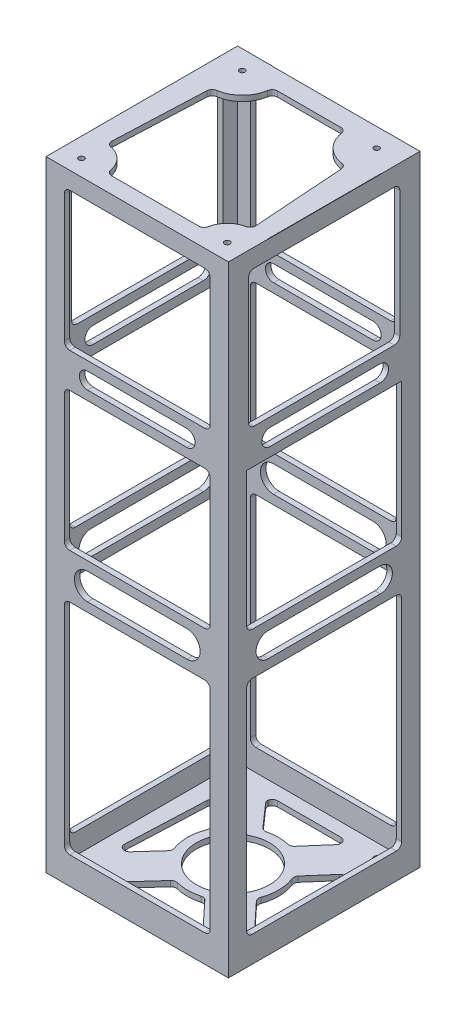
SolidWorks part; units mm, degrees
material "1060 Alloy"
ref_plane "Front Plane" through (0, 0, 0) normal (0, 0, 1) x (1, 0, 0)
ref_plane "Top Plane" through (0, 0, 0) normal (0, 1, 0) x (1, 0, 0)
ref_plane "Right Plane" through (0, 0, 0) normal (1, 0, 0) x (0, 0, -1)
sketch "Sketch1" plane through (0, 0, 0) normal (0, 1, 0) x (1, 0, 0)
  line L1 (-50, -52.5) -> (50, -52.5)
  line L2 (-50, -52.5) -> (-50, 52.5)
  line L3 (-50, 52.5) -> (50, 52.5)
  line L4 (50, -52.5) -> (50, 52.5)
  line L5 (-50, -52.5) -> (50, 52.5) construction
  line L6 (-50, 52.5) -> (50, -52.5) construction
  point P0 (0, 0)
  dimension "D1" = 100
  dimension "D2" = 105
extrude "Body" add sketch "Sketch1" along normal blind 337
shell "Shell1" thickness 3 removed face at (0, 0, 0)
sketch "Sketch8" plane through (0, 0, 0) normal (0, -1, 0) x (1, 0, 0)
  line L1 (-50, 52.5) -> (50, 52.5)
  line L2 (-50, 52.5) -> (-50, -52.5)
  line L3 (-50, -52.5) -> (50, -52.5)
  line L4 (50, 52.5) -> (50, -52.5)
  line L5 (-50, 52.5) -> (50, -52.5) construction
  line L6 (-50, -52.5) -> (50, 52.5) construction
  circle A0 centre (0, 0) radius 20
  point P4 (0, 0)
  dimension "D1" = 40
extrude "ScopeEnd" add sketch "Sketch8" along normal blind 3
sketch "Sketch5" plane through (0, 334, 0) normal (0, -1, 0) x (1, 0, 0)
  line L0 (49.9999, -52.4997) -> (-50.0001, 52.5003) construction
  line L1 (-50.0001, 52.5003) -> (-50.0001, -52.4997) construction
  line L2 (-50.0001, -52.4997) -> (49.9999, 52.5003) construction
  line L5 (45.6309, 48.6491) -> (-44.5391, -47.2409) construction
  line L6 (52.5, 50.0002) -> (52.5, -49.9998) construction
  line L7 (50, -52.4998) -> (50, 52.5002) construction
  line L8 (50, 52.5002) -> (-50, 52.5002) construction
  line L9 (-50, -52.4998) -> (-50, 52.5002) construction
  line L10 (50, -52.4998) -> (-50, 52.5002) construction
  line L11 (50, 52.5002) -> (-50, -52.4998) construction
  line L12 (-44.5391, -47.2409) -> (-44.5391, 48.6491) construction
  line L13 (0, 0.0002) -> (0, -67.3948) construction
  circle A0 centre (36.6309, -42.1409) radius 1.5
  circle A1 centre (-37.0391, -42.1409) radius 1.5
  circle A2 centre (-39.4391, 43.6491) radius 1.5
  circle A3 centre (40.5309, 43.6491) radius 1.5
  point P4 (-0.0001, 0.0003)
  point P17 (0, 0.0002)
  dimension "D1" = 3
  dimension "D2" = 3
extrude "AluHoles" cut sketch "Sketch5" against normal through all both and the other way through all
sketch "Sketch6" plane through (0, 337, 0) normal (0, 1, 0) x (1, 0, 0)
  line L0 (-37.0391, 25.5488) -> (-39.4391, -29.8697)
  line L1 (-25.6597, -43.6491) -> (27.5694, -43.6491)
  line L2 (-20.447, 42.1409) -> (19.7181, 42.1409)
  line L3 (36.6309, 25.2281) -> (40.5309, -30.6876)
  arc A0 (-37.0391, 25.5488) -> (-20.447, 42.1409) centre (-37.0391, 42.1409) ccw
  arc A1 (19.7181, 42.1409) -> (36.6309, 25.2281) centre (36.6309, 42.1409) ccw
  arc A2 (40.5309, -30.6876) -> (27.5694, -43.6491) centre (40.5309, -43.6491) ccw
  arc A3 (-25.6597, -43.6491) -> (-39.4391, -29.8697) centre (-39.4391, -43.6491) ccw
extrude "Cut-Extrude3" cut sketch "Sketch6" against normal blind 3
fillet "Fillet1" radius 3 8 edges at (-39.4391, 335.5, 29.8697) (-25.6597, 335.5, 43.6491) (27.5694, 335.5, 43.6491) (40.5309, 335.5, 30.6876) (36.6309, 335.5, -25.2281) (19.7181, 335.5, -42.1409) (-37.0391, 335.5, -25.5488) (-20.447, 335.5, -42.1409)
sketch "Sketch9" plane through (0, 0, 52.5) normal (0, 0, 1) x (1, 0, 0)
  line L1 (-50, 337) -> (50, 337) construction
  line L2 (-50, 337) -> (-50, -3) construction
  line L3 (-50, -3) -> (50, -3) construction
  line L4 (50, 337) -> (50, -3) construction
  line L5 (-50, 337) -> (50, -3) construction
  line L6 (-50, -3) -> (50, 337) construction
  line L7 (-50, 337) -> (50, 337) construction
  line L8 (-50, 337) -> (-50, 242) construction
  line L9 (-50, 242) -> (50, 242) construction
  line L10 (50, 337) -> (50, 242) construction
  line L11 (-50, 337) -> (50, 242) construction
  line L12 (-50, 242) -> (50, 337) construction
  line L13 (-50, 242) -> (50, 242)
  line L14 (-50, 242) -> (-50, 147) construction
  line L15 (-50, 147) -> (50, 147) construction
  line L16 (50, 242) -> (50, 147) construction
  line L17 (-50, 242) -> (50, 147) construction
  line L18 (-50, 147) -> (50, 242) construction
  line L19 (-50, 147) -> (50, 147) construction
  line L20 (-50, 147) -> (-50, -3) construction
  line L21 (-50, -3) -> (50, -3) construction
  line L22 (50, 147) -> (50, -3) construction
  line L23 (-50, 147) -> (50, -3) construction
  line L24 (-50, -3) -> (50, 147) construction
  line L25 (-40, 251.5) -> (40, 251.5)
  line L26 (-40, 251.5) -> (-40, 327.5)
  line L27 (-40, 327.5) -> (40, 327.5)
  line L28 (40, 251.5) -> (40, 327.5)
  line L29 (-40, 251.5) -> (40, 327.5) construction
  line L30 (-40, 327.5) -> (40, 251.5) construction
  line L31 (-40, 156.5) -> (40, 156.5)
  line L32 (-40, 156.5) -> (-40, 232.5)
  line L33 (-40, 232.5) -> (40, 232.5)
  line L34 (40, 156.5) -> (40, 232.5)
  line L35 (-40, 156.5) -> (40, 232.5) construction
  line L36 (-40, 232.5) -> (40, 156.5) construction
  line L37 (-40, 12) -> (40, 12)
  line L38 (-40, 12) -> (-40, 132)
  line L39 (-40, 132) -> (40, 132)
  line L40 (40, 12) -> (40, 132)
  line L41 (-40, 12) -> (40, 132) construction
  line L42 (-40, 132) -> (40, 12) construction
  point P4 (0, 167)
  point P9 (0, 289.5)
  point P12 (0, 194.5)
  point P13 (0, 289.5)
  point P14 (0, 72)
  point P19 (0, 194.5)
  point P24 (0, 72)
  dimension "D1" = 150
  dimension "D2" = 95
  dimension "D3" = 95
  dimension "D4" = 10
  dimension "D5" = 10
  dimension "D6" = 10
extrude "Cut-Extrude4" cut sketch "Sketch9" against normal through all contours L31 L34 L33 L32 | L25 L28 L27 L26 | L37 L40 L39 L38 region at (0, 289.5, 52.5) region at (0, 194.5, 52.5) region at (0, 72, 52.5)
sketch "Sketch10" plane through (50, 0, 0) normal (1, 0, 0) x (0, 0, -1)
  line L0 (52.5, 337) -> (52.5, -3) construction
  line L1 (-52.5, 337) -> (52.5, 337) construction
  line L2 (-52.5, 337) -> (-52.5, 242) construction
  line L3 (-52.5, 242) -> (52.5, 242) construction
  line L4 (52.5, 337) -> (52.5, 242) construction
  line L5 (-52.5, 337) -> (52.5, 242) construction
  line L6 (-52.5, 242) -> (52.5, 337) construction
  line L7 (-52.5, 337) -> (-52.5, -3) construction
  line L8 (52.5, 242) -> (-52.5, 242) construction
  line L9 (52.5, 242) -> (52.5, 147) construction
  line L10 (52.5, 147) -> (-52.5, 147) construction
  line L11 (-52.5, 242) -> (-52.5, 147) construction
  line L12 (52.5, 242) -> (-52.5, 147) construction
  line L13 (52.5, 147) -> (-52.5, 242) construction
  line L15 (42.5, 156.0476) -> (-42.5, 156.0476)
  line L16 (42.5, 156.0476) -> (42.5, 232.9524)
  line L17 (42.5, 232.9524) -> (-42.5, 232.9524)
  line L18 (-42.5, 156.0476) -> (-42.5, 232.9524)
  line L19 (42.5, 156.0476) -> (-42.5, 232.9524) construction
  line L20 (42.5, 232.9524) -> (-42.5, 156.0476) construction
  line L21 (41.4474, 252) -> (-41.4474, 252)
  line L22 (41.4474, 252) -> (41.4474, 327)
  line L23 (41.4474, 327) -> (-41.4474, 327)
  line L24 (-41.4474, 252) -> (-41.4474, 327)
  line L25 (41.4474, 252) -> (-41.4474, 327) construction
  line L26 (41.4474, 327) -> (-41.4474, 252) construction
  line L27 (-52.5, 147) -> (52.5, 147) construction
  line L28 (-52.5, 147) -> (-52.5, -3) construction
  line L29 (-52.5, -3) -> (52.5, -3) construction
  line L30 (52.5, 147) -> (52.5, -3) construction
  line L31 (-52.5, 147) -> (52.5, -3) construction
  line L32 (-52.5, -3) -> (52.5, 147) construction
  line L33 (-42.5, 11.2857) -> (42.5, 11.2857)
  line L34 (-42.5, 11.2857) -> (-42.5, 132.7143)
  line L35 (-42.5, 132.7143) -> (42.5, 132.7143)
  line L36 (42.5, 11.2857) -> (42.5, 132.7143)
  line L37 (-42.5, 11.2857) -> (42.5, 132.7143) construction
  line L38 (-42.5, 132.7143) -> (42.5, 11.2857) construction
  point P4 (0, 289.5)
  point P10 (0, 194.5)
  point P13 (0, 194.5)
  point P18 (0, 289.5)
  point P25 (0, 72)
  point P27 (0, 72)
  dimension "D1" = 95
  dimension "D2" = 95
  dimension "D3" = 10
  dimension "D4" = 10
extrude "Cut-Extrude5" cut sketch "Sketch10" against normal through all
fillet "Fillet2" radius 3 45 edges at (-48.5, 132.7143, -42.5) (-48.5, 11.2857, 42.5) (48.5, 11.2857, 42.5) (40, 12, 51) (48.5, 11.2857, -42.5) (40, 12, -51) (48.5, 132.7143, -42.5) (40, 132, 51) (40, 132, -51) (-40, 132, -51) (-40, 132, 51) (-48.5, 132.7143, 42.5) (48.5, 132.7143, 42.5) (-48.5, 232.9524, -42.5) (40, 232.5, -51) (-40, 232.5, -51) (-40, 156.5, -51) (48.5, 156.0476, 42.5) (-48.5, 156.0476, 42.5) (-48.5, 11.2857, -42.5) (-48.5, 156.0476, -42.5) (40, 156.5, -51) (48.5, 156.0476, -42.5) (40, 156.5, 51) (-40, 156.5, 51) (-40, 232.5, 51) (40, 232.5, 51) (40, 327.5, 51) (48.5, 252, -41.4474) (-48.5, 252, -41.4474) (-40, 251.5, -51) (40, 251.5, -51) (40, 251.5, 51) (40, 327.5, -51) (48.5, 327, -41.4474) (-48.5, 327, -41.4474) (-40, 327.5, -51) (-48.5, 327, 41.4474) (48.5, 327, 41.4474) (-40, 327.5, 51) (-48.5, 252, 41.4474) (-40, 251.5, 51) (48.5, 252, 41.4474) (-40, 12, 51) (-40, 12, -51)
sketch "Sketch11" plane through (0, 0, -52.5) normal (0, 0, -1) x (-1, 0, 0)
  line L0 (-31.11, 337) -> (31.11, 337) construction
  line L1 (-50, 337) -> (50, 337) construction
  line L2 (0, 0) -> (0, 50000) construction
  line L3 (-31.11, 337) -> (31.11, 337)
  line L4 (-31.11, 337) -> (-31.11, 336.9)
  line L5 (-31.11, 336.9) -> (31.11, 336.9)
  line L6 (31.11, 337) -> (31.11, 336.9)
  line L7 (-31.11, 337) -> (31.11, 336.9) construction
  line L8 (-31.11, 336.9) -> (31.11, 337) construction
  point P5 (0, 337)
  point P7 (0, 336.95)
  dimension "D1" = 62.22
  dimension "D2" = 0.1
  dimension "D3" = 0
extrude "Cut-Extrude6" cut sketch "Sketch11" against normal blind 0.1
sketch "Sketch12" plane through (50, 0, 0) normal (1, 0, 0) x (0, 0, -1)
  line L0 (-31.11, 337) -> (31.11, 337) construction
  line L1 (-52.5, 337) -> (52.5, 337) construction
  line L2 (0, 0) -> (0, 50000) construction
  line L4 (-31.11, 337) -> (31.11, 337)
  line L5 (-31.11, 337) -> (-31.11, 336.9)
  line L6 (-31.11, 336.9) -> (31.11, 336.9)
  line L7 (31.11, 337) -> (31.11, 336.9)
  line L8 (-31.11, 337) -> (31.11, 336.9) construction
  line L9 (-31.11, 336.9) -> (31.11, 337) construction
  point P5 (0, 337)
  point P10 (0, 336.95)
  dimension "D1" = 62.22
  dimension "D2" = 0
  dimension "D3" = 0.1
extrude "Cut-Extrude7" cut sketch "Sketch12" against normal blind 0.1
sketch "Sketch13" plane through (0, 0, -52.5) normal (0, 0, -1) x (-1, 0, 0)
  line L0 (-27.2161, 242) -> (27.2161, 242) construction
  line L1 (-37, 156.5) -> (37, 156.5) construction
  line L2 (-37, 156.5) -> (-37, 132) construction
  line L3 (-37, 132) -> (37, 132) construction
  line L4 (37, 156.5) -> (37, 132) construction
  line L5 (-37, 156.5) -> (37, 132) construction
  line L6 (-37, 132) -> (37, 156.5) construction
  line L7 (-37, 251.5) -> (37, 251.5) construction
  line L8 (-37, 251.5) -> (-37, 232.5) construction
  line L9 (-37, 232.5) -> (37, 232.5) construction
  line L10 (37, 251.5) -> (37, 232.5) construction
  line L11 (-37, 251.5) -> (37, 232.5) construction
  line L12 (-37, 232.5) -> (37, 251.5) construction
  line L13 (-27.2161, 246.5) -> (27.2161, 246.5)
  line L14 (-27.2161, 237.5) -> (27.2161, 237.5)
  line L15 (-27.2161, 144.25) -> (27.2161, 144.25) construction
  line L16 (-27.2161, 151.5) -> (27.2161, 151.5)
  line L17 (-27.2161, 137) -> (27.2161, 137)
  arc A0 (-27.2161, 246.5) -> (-27.2161, 237.5) centre (-27.2161, 242) ccw
  arc A1 (27.2161, 237.5) -> (27.2161, 246.5) centre (27.2161, 242) ccw
  arc A2 (-27.2161, 151.5) -> (-27.2161, 137) centre (-27.2161, 144.25) ccw
  arc A3 (27.2161, 137) -> (27.2161, 151.5) centre (27.2161, 144.25) ccw
  point P4 (0, 144.25)
  point P11 (0, 242)
  point P16 (0, 242)
  point P22 (0, 144.25)
  dimension "D1" = 5
  dimension "D2" = 5
extrude "Cut-Extrude8" cut sketch "Sketch13" against normal through all
sketch "Sketch14" plane through (50, 0, 0) normal (1, 0, 0) x (0, 0, -1)
  line L0 (42.5, 232.9524) -> (-42.5, 232.9524) construction
  line L1 (-38.4474, 252) -> (39.5, 252) construction
  line L2 (-38.4474, 252) -> (-38.4474, 232.9524) construction
  line L3 (-38.4474, 232.9524) -> (39.5, 232.9524) construction
  line L4 (39.5, 252) -> (39.5, 232.9524) construction
  line L5 (-38.4474, 252) -> (39.5, 232.9524) construction
  line L6 (-38.4474, 232.9524) -> (39.5, 252) construction
  line L7 (-29.6655, 242.4762) -> (30.7181, 242.4762) construction
  line L8 (-39.5, 156.0476) -> (39.5, 156.0476) construction
  line L9 (-39.5, 156.0476) -> (-39.5, 132.7143) construction
  line L10 (-39.5, 132.7143) -> (39.5, 132.7143) construction
  line L11 (39.5, 156.0476) -> (39.5, 132.7143) construction
  line L12 (-39.5, 156.0476) -> (39.5, 132.7143) construction
  line L13 (-39.5, 132.7143) -> (39.5, 156.0476) construction
  line L14 (-29.6655, 247) -> (30.7181, 247)
  line L15 (-29.6655, 237.9524) -> (30.7181, 237.9524)
  line L16 (-30.7181, 144.381) -> (30.7181, 144.381) construction
  line L17 (-30.7181, 151.0476) -> (30.7181, 151.0476)
  line L18 (-30.7181, 137.7143) -> (30.7181, 137.7143)
  arc A0 (42.5, 229.9524) -> (39.5, 232.9524) centre (39.5, 229.9524) ccw construction
  arc A1 (-29.6655, 247) -> (-29.6655, 237.9524) centre (-29.6655, 242.4762) ccw
  arc A2 (30.7181, 237.9524) -> (30.7181, 247) centre (30.7181, 242.4762) ccw
  arc A3 (-30.7181, 151.0476) -> (-30.7181, 137.7143) centre (-30.7181, 144.381) ccw
  arc A4 (30.7181, 137.7143) -> (30.7181, 151.0476) centre (30.7181, 144.381) ccw
  point P4 (0.5263, 242.4762)
  point P15 (0, 144.381)
  point P20 (0.5263, 242.4762)
  point P26 (0, 144.381)
  dimension "D1" = 5
  dimension "D2" = 5
extrude "Cut-Extrude9" cut sketch "Sketch14" against normal through all
sketch "Sketch15" plane through (0, -3, 0) normal (0, -1, 0) x (1, 0, 0)
  line L0 (-39.4391, 29.8697) -> (-37.0391, -25.5488)
  line L1 (-39.4391, 43.6491) -> (-16.7604, 18.5496) construction
  line L2 (-20.447, -42.1409) -> (19.7181, -42.1409)
  line L3 (-25.6636, 43.3192) -> (-7.9414, 23.7052)
  line L4 (36.6309, -25.2281) -> (40.5309, 30.6876)
  line L5 (-39.3874, 28.6758) -> (-22.781, 10.2968)
  line L6 (27.5694, 43.6491) -> (-25.6597, 43.6491)
  line L7 (40.5309, 43.6491) -> (17.0112, 18.3199) construction
  line L8 (40.4001, 28.812) -> (22.919, 9.986)
  line L9 (26.8846, 43.6491) -> (8.2631, 23.595)
  line L20 (22.5791, -10.7325) -> (35.2299, -25.2862)
  line L21 (16.4011, -18.8681) -> (36.6309, -42.1409) construction
  line L22 (7.4846, -23.8533) -> (20.1354, -38.4071)
  line L23 (-7.6154, -23.8119) -> (-20.7872, -38.798)
  line L24 (-16.5044, -18.7778) -> (-37.0391, -42.1409) construction
  line L25 (-22.6376, -10.6083) -> (-35.8095, -25.5945)
  arc A0 (-7.6154, -23.8119) -> (7.4846, -23.8533) centre (0, 0) ccw
  circle A1 centre (0, 0) radius 20 construction
  arc A2 (20.1354, -38.4071) -> (19.7181, -42.1409) centre (36.6309, -42.1409) ccw
  arc A3 (-35.8095, -25.5945) -> (-37.0391, -25.5488) centre (-37.0391, -42.1409) ccw
  arc A4 (36.6309, -25.2281) -> (35.2299, -25.2862) centre (36.6309, -42.1409) ccw
  arc A5 (-20.447, -42.1409) -> (-20.7872, -38.798) centre (-37.0391, -42.1409) ccw
  arc A6 (-25.6636, 43.3192) -> (-25.6597, 43.6491) centre (-39.4391, 43.6491) ccw
  arc A7 (22.5791, -10.7325) -> (22.919, 9.986) centre (0, 0) ccw
  arc A8 (8.2631, 23.595) -> (-7.9414, 23.7052) centre (0, 0) ccw
  arc A9 (-22.781, 10.2968) -> (-22.6376, -10.6083) centre (0, 0) ccw
  point P6 (-19.7195, 21.8245)
  point P30 (20.2655, 21.8245)
  point P36 (18.3155, -21.0705)
  point P42 (-18.5195, -21.0705)
  dimension "D1" = 5
extrude "Cut-Extrude10" cut sketch "Sketch15" against normal blind 10 contours A9 L5 L0 A3 L25 | A8 L9 L6 A6 L3 | A7 L20 A4 L4 L8 | A5 L2 A2 L22 A0 L23 region at (-32.0753, -3, 0.7548) region at (-0.1907, -3, -34.6295) region at (0.3682, -3, 35.6611) region at (32.2604, -3, 0.8709)
fillet "Fillet3" radius 3 21 edges at (-37.0391, -1.5, -25.5488) (-35.8095, -1.5, -25.5945) (-22.781, -1.5, 10.2968) (-22.6376, -1.5, -10.6083) (20.1354, -1.5, -38.4071) (19.7181, -1.5, -42.1409) (7.4846, -1.5, -23.8533) (-7.6154, -1.5, -23.8119) (-20.7872, -1.5, -38.798) (-20.447, -1.5, -42.1409) (22.5791, -1.5, -10.7325) (36.6309, -1.5, -25.2281) (35.2299, -1.5, -25.2862) (8.2631, -1.5, 23.595) (-7.9414, -1.5, 23.7052) (22.919, -1.5, 9.986) (-39.3874, -1.5, 28.6758) (40.4001, -1.5, 28.812) (26.8846, -1.5, 43.6491) (-25.6597, -1.5, 43.6491) (-25.6636, -1.5, 43.3192)
